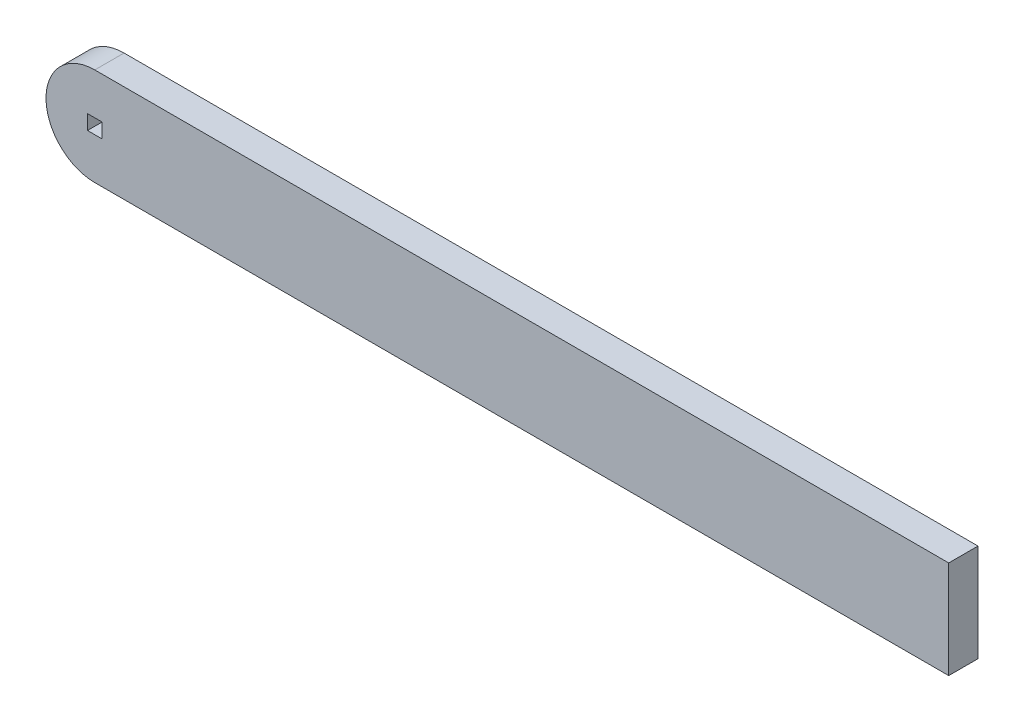
SolidWorks part; units mm, degrees
ref_plane "Front Plane" through (0, 0, 0) normal (0, 0, 1) x (1, 0, 0)
ref_plane "Top Plane" through (0, 0, 0) normal (0, 1, 0) x (1, 0, 0)
ref_plane "Right Plane" through (0, 0, 0) normal (1, 0, 0) x (0, 0, -1)
sketch "Sketch1" plane through (0, 0, 0) normal (0, 0, 1) x (1, 0, 0)
  line L1 (0, 0) -> (185, 0)
  line L2 (0, 0) -> (0, 20)
  line L3 (0, 20) -> (185, 20)
  line L4 (185, 0) -> (185, 20)
  dimension "D1" = 20
  dimension "D2" = 185
extrude "Boss-Extrude1" add sketch "Sketch1" along normal blind 6
sketch "Sketch2" plane through (0, 0, 6) normal (0, 0, 1) x (1, 0, 0)
  line L1 (8.5, 11.5) -> (11.5, 11.5)
  line L2 (8.5, 11.5) -> (8.5, 8.5)
  line L3 (8.5, 8.5) -> (11.5, 8.5)
  line L4 (11.5, 11.5) -> (11.5, 8.5)
  line L5 (8.5, 11.5) -> (11.5, 8.5) construction
  line L7 (0, 20) -> (0, 0) construction
  point P7 (10, 10)
  point P8 (0, 10)
  dimension "D1" = 3
  dimension "D2" = 3
  dimension "D3" = 10
extrude "Cut-Extrude2" cut sketch "Sketch2" against normal through all
fillet "Fillet1" radius 10 2 edges at (0, 0, 3) (0, 20, 3)
